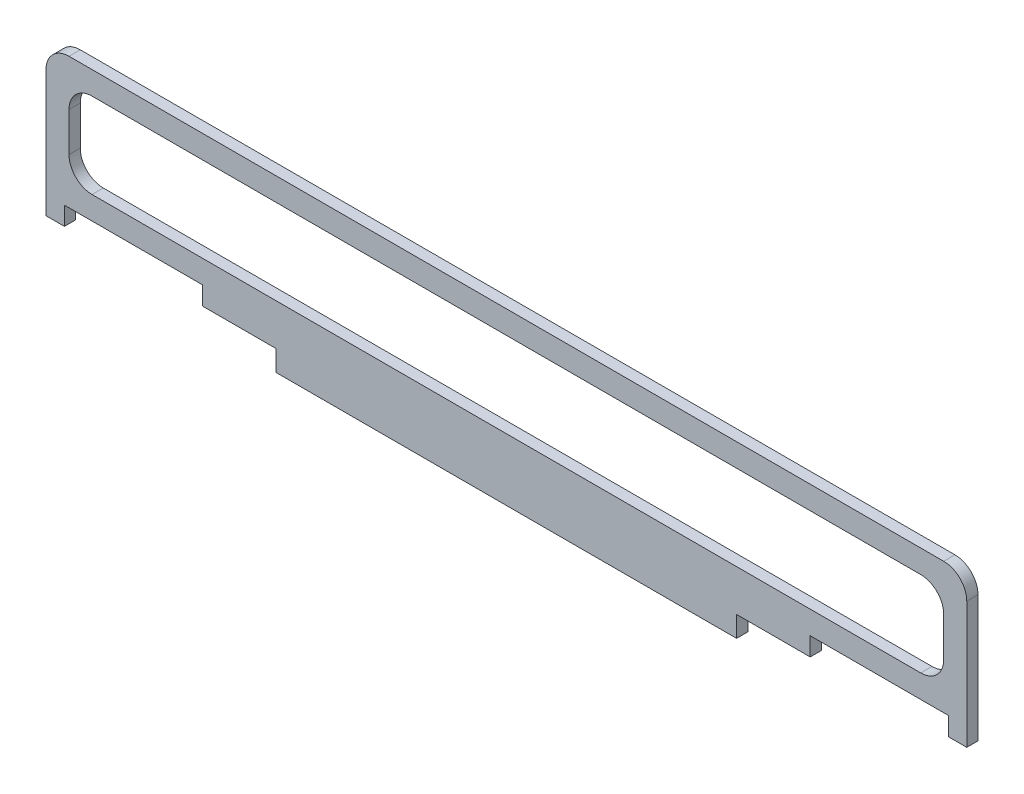
SolidWorks part; units mm, degrees
ref_plane "Front Plane" through (0, 0, 0) normal (0, 0, 1) x (1, 0, 0)
ref_plane "Top Plane" through (0, 0, 0) normal (0, 1, 0) x (1, 0, 0)
ref_plane "Right Plane" through (0, 0, 0) normal (1, 0, 0) x (0, 0, -1)
sketch "Sketch1" plane through (0, 0, 0) normal (0, 0, 1) x (1, 0, 0)
  line L1 (-127, 23.495) -> (127, 23.495)
  line L2 (-127, 23.495) -> (-127, -23.495)
  line L3 (-127, -23.495) -> (127, -23.495)
  line L4 (127, 23.495) -> (127, -23.495)
  line L5 (-127, 23.495) -> (127, -23.495) construction
  line L6 (-127, -23.495) -> (127, 23.495) construction
  point P0 (0, 0)
  dimension "D1" = 46.99
  dimension "D2" = 254
extrude "Boss-Extrude1" add sketch "Sketch1" along normal blind 3.0988
fillet "Fillet1" radius 6.35 2 edges at (127, 23.495, 1.5494) (-127, 23.495, 1.5494)
sketch "Sketch2" plane through (0, 0, 3.0988) normal (0, 0, 1) x (1, 0, 0)
  line L0 (0, -1.7043) -> (0, 1.7043) construction
  line L1 (-127, -23.495) -> (-63.5, -23.495)
  line L2 (-127, -23.495) -> (-127, -17.78)
  line L3 (-127, -17.78) -> (-63.5, -17.78)
  line L4 (-63.5, -23.495) -> (-63.5, -17.78)
  line L5 (63.5, -23.495) -> (63.5, -17.78)
  line L6 (127, -17.78) -> (63.5, -17.78)
  line L7 (127, -23.495) -> (127, -17.78)
  line L8 (127, -23.495) -> (63.5, -23.495)
  dimension "D1" = 63.5
  dimension "D2" = 5.715
extrude "Cut-Extrude1" cut sketch "Sketch2" against normal through all
sketch "Sketch3" plane through (0, 0, 3.0988) normal (0, 0, 1) x (1, 0, 0)
  line L0 (-63.5, -17.78) -> (-127, -17.78) construction
  line L1 (-121.92, -17.78) -> (-83.82, -17.78)
  line L2 (-121.92, -17.78) -> (-121.92, -12.7)
  line L3 (-121.92, -12.7) -> (-83.82, -12.7)
  line L4 (-83.82, -17.78) -> (-83.82, -12.7)
  line L5 (-127, 17.145) -> (-127, -17.78) construction
  line L6 (0, -1.7043) -> (0, 1.7043) construction
  line L7 (83.82, -17.78) -> (83.82, -12.7)
  line L8 (121.92, -12.7) -> (83.82, -12.7)
  line L9 (121.92, -17.78) -> (121.92, -12.7)
  line L10 (121.92, -17.78) -> (83.82, -17.78)
  dimension "D1" = 38.1
  dimension "D2" = 5.08
  dimension "D3" = 5.08
extrude "Cut-Extrude2" cut sketch "Sketch3" against normal through all
sketch "Sketch4" plane through (0, 0, 3.0988) normal (0, 0, 1) x (1, 0, 0)
  line L16 (-77.47, -6.35) -> (77.47, -6.35)
  line L32 (-120.65, -6.35) -> (-77.47, -6.35)
  line L33 (-77.47, -6.35) -> (-77.47, -11.43)
  line L34 (-77.47, -11.43) -> (-57.15, -11.43)
  line L35 (-57.15, -11.43) -> (-57.15, -17.145)
  line L36 (-57.15, -17.145) -> (57.15, -17.145)
  line L37 (57.15, -17.145) -> (57.15, -11.43)
  line L38 (57.15, -11.43) -> (77.47, -11.43)
  line L39 (77.47, -11.43) -> (77.47, -6.35)
  line L40 (77.47, -6.35) -> (120.65, -6.35)
  line L41 (120.65, -6.35) -> (120.65, 17.145)
  line L42 (120.65, 17.145) -> (-120.65, 17.145)
  line L43 (-120.65, 17.145) -> (-120.65, -6.35)
  line L44 (-120.65, -6.35) -> (-77.47, -6.35)
  line L52 (77.47, -6.35) -> (120.65, -6.35)
  line L53 (120.65, -6.35) -> (120.65, 17.145)
  line L54 (120.65, 17.145) -> (-120.65, 17.145)
  line L55 (-120.65, 17.145) -> (-120.65, -6.35)
  dimension "D1" = 6.35
extrude "Cut-Extrude3" cut sketch "Sketch4" against normal through all
fillet "Fillet2" radius 6.35 4 edges at (120.65, -6.35, 1.5494) (120.65, 17.145, 1.5494) (-120.65, 17.145, 1.5494) (-120.65, -6.35, 1.5494)
equation "\"motor offset\"= 6mm"
equation "\"thickness0.25\"= 0.225in"
equation "\"thickness0.125\"= 0.122in"
